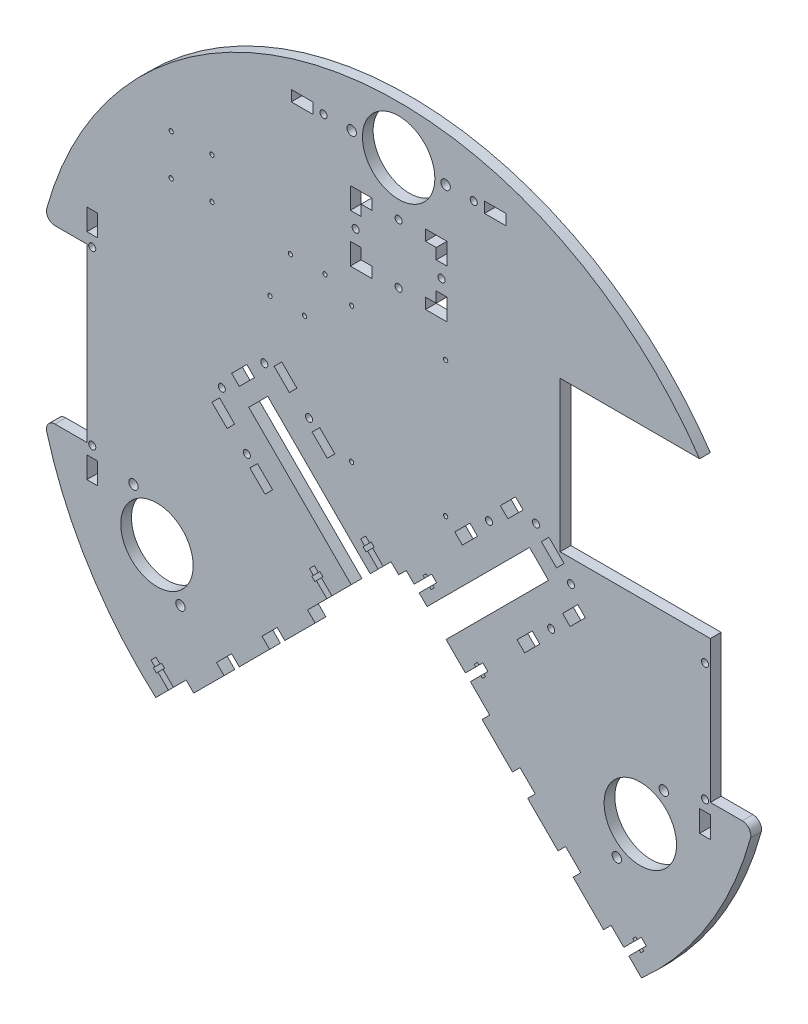
SolidWorks part; units mm, degrees
ref_plane "Front Plane" through (0, 0, 0) normal (0, 0, 1) x (1, 0, 0)
ref_plane "Top Plane" through (0, 0, 0) normal (0, 1, 0) x (1, 0, 0)
ref_plane "Right Plane" through (0, 0, 0) normal (1, 0, 0) x (0, 0, -1)
sketch "Sketch1" plane through (0, 0, 0) normal (0, 0, 1) x (1, 0, 0)
  circle A0 centre (0, 0) radius 215.9
  dimension "D1" = 431.8
extrude "Base Plate Extrusion" add sketch "Sketch1" along normal blind 6.35
sketch "Sketch2" plane through (0, 0, 6.35) normal (0, 0, 1) x (1, 0, 0)
  line L0 (0, 0) -> (0, -230.9791) construction
  line L1 (0, -17.4608) -> (143.6841, -161.1449)
  line L2 (0, -17.4608) -> (-143.6841, -161.1449)
  circle A1 centre (0, 0) radius 215.9 construction
  arc A2 (143.6841, -161.1449) -> (-143.6841, -161.1449) centre (0, 0) cw
  dimension "D1" = 90
  dimension "D2" = 203.2
extrude "V Funnel Cut" cut sketch "Sketch2" against normal through all
sketch "Sketch3" plane through (0, 0, 6.35) normal (0, 0, 1) x (1, 0, 0)
  line L0 (0, 0) -> (251.7982, 0) construction
  line L1 (209.8384, 50.8) -> (184.4384, 50.8)
  line L2 (209.8384, 50.8) -> (209.8384, -50.8)
  line L3 (209.8384, -50.8) -> (184.4384, -50.8)
  line L4 (184.4384, 50.8) -> (184.4384, -50.8)
  arc A0 (143.6841, -161.1449) -> (-143.6841, -161.1449) centre (0, 0) ccw construction
  arc A1 (209.8384, 50.8) -> (209.8384, -50.8) centre (0, 0) cw
  arc M7 (143.6841, -161.1449) -> (-143.6841, -161.1449) centre (0, 0) ccw
  dimension "D1" = 25.4
  dimension "D2" = 101.6
extrude "Wheel Track Cut" cut sketch "Sketch3" against normal through all contours L2 L0 A1 | L4 L0 L2 L1 | L0 L4 L3 L2 | L0 L2 M7 region at (197.1384, 25.4, 6.35) region at (197.1384, -25.4, 6.35) region at (212.266, 19.0862, 6.35) region at (212.266, -19.0862, 6.35)
mirror "Wheel Track Cut Mirror" about plane through (0, 0, 0) normal (1, 0, 0) of "Wheel Track Cut"
sketch "Sketch4" plane through (0, 0, 6.35) normal (0, 0, 1) x (1, 0, 0)
  line L0 (88.68, 15.0926) -> (77.4547, 26.3179)
  line L1 (88.68, 15.0926) -> (28.0633, -45.5241)
  line L2 (77.4547, 26.3179) -> (16.838, -34.2988)
  line L3 (28.0633, -45.5241) -> (16.838, -34.2988)
  line L4 (84.3174, 21.9553) -> (56.956, -5.4061) construction
  line L5 (65.1069, -1.7454) -> (69.5826, 2.7303) construction
  line L6 (65.0924, 7.2204) -> (60.6167, 2.7447) construction
  line L7 (143.6841, -161.1449) -> (0, -17.4608) construction
  dimension "D1" = 15.875
  dimension "D2" = 85.725
extrude "Silo Picker Clearance" cut sketch "Sketch4" against normal through all
sketch "Sketch5" plane through (0, 0, 6.35) normal (0, 0, 1) x (1, 0, 0)
  line L0 (-4.4901, -21.951) -> (0, -17.4608)
  line L1 (-4.4901, -21.951) -> (0, -26.4411)
  line L2 (0, -17.4608) -> (4.4901, -21.951)
  line L3 (0, -26.4411) -> (4.4901, -21.951)
  line L4 (0, -17.4608) -> (-143.6841, -161.1449) construction
  line L6 (4.4901, -21.951) -> (0, -26.4411) construction
  dimension "D1" = 6.35
extrude "V Funnel Corner" add sketch "Sketch5" against normal up to surface (6.35 mm away) up to face at (14.0691, -14.8765, 0)
mirror "Dump Picker Clearance" about plane through (0, 0, 0) normal (1, 0, 0) of "Silo Picker Clearance"
sketch "Sketch6" plane through (8.7304, -8.7304, 0) normal (0.7071, -0.7071, 0) x (0, 0, -1)
  line L0 (-6.35, -52.0342) -> (-6.35, -215.5467) construction
  line L1 (-6.35, -190.1467) -> (0, -190.1467)
  line L2 (-6.35, -190.1467) -> (-6.35, -164.7467)
  line L3 (-6.35, -164.7467) -> (0, -164.7467)
  line L4 (0, -190.1467) -> (0, -164.7467)
  line L5 (0, -52.0342) -> (0, -215.5467) construction
  dimension "D1" = 25.4
  dimension "D2" = 25.4
extrude "V Funnel Tab Left" add sketch "Sketch6" along normal blind 6.35
pattern_linear "V Funnel Tab Pattern Left" count 3 spacing 38.1 along (0.7071, 0.7071, 0) of "V Funnel Tab Left"
sketch "Sketch7" plane through (-8.7304, -8.7304, 0) normal (-0.7071, -0.7071, 0) x (0, 0, 1)
  line L0 (6.35, -215.5467) -> (6.35, -52.0342) construction
  line L1 (6.35, -164.7467) -> (0, -164.7467)
  line L2 (6.35, -164.7467) -> (6.35, -190.1467)
  line L3 (6.35, -190.1467) -> (0, -190.1467)
  line L4 (0, -164.7467) -> (0, -190.1467)
  line L5 (0, -215.5467) -> (0, -52.0342) construction
  dimension "D1" = 25.4
  dimension "D2" = 25.4
extrude "V Funnel Tab Right" add sketch "Sketch7" along normal blind 6.35
pattern_linear "V Funnel Tab Pattern Right" count 3 spacing 38.1 along (-0.7071, 0.7071, 0) of "V Funnel Tab Right"
sketch "Sketch8" plane through (0, 0, 0) normal (0, 0, -1) x (-1, 0, 0)
  line L0 (-70.046, -24.645) -> (-79.0263, -15.6648)
  line L1 (-79.0263, -15.6648) -> (-83.5164, -20.1549)
  line L2 (-83.5164, -20.1549) -> (-74.5361, -29.1352)
  line L3 (-74.5361, -29.1352) -> (-70.046, -24.645)
  line L4 (-96.9868, 2.2957) -> (-101.4769, -2.1944)
  line L5 (-101.4769, -2.1944) -> (-110.4572, 6.7859)
  line L6 (-110.4572, 6.7859) -> (-105.967, 11.276)
  line L7 (-105.967, 11.276) -> (-96.9868, 2.2957)
  line L8 (-97.8965, 28.3267) -> (-88.9163, 37.307)
  line L9 (-88.9163, 37.307) -> (-84.4262, 32.8169)
  line L10 (-84.4262, 32.8169) -> (-93.4064, 23.8366)
  line L11 (-93.4064, 23.8366) -> (-97.8965, 28.3267)
  line L12 (-64.6578, 34.6246) -> (-60.1677, 39.1148)
  line L13 (-60.1677, 39.1148) -> (-69.148, 48.095)
  line L14 (-69.148, 48.095) -> (-73.6381, 43.6049)
  line L15 (-73.6381, 43.6049) -> (-64.6578, 34.6246)
  line L16 (-46.6973, 16.6641) -> (-42.2072, 21.1543)
  line L17 (-42.2072, 21.1543) -> (-33.2269, 12.174)
  line L18 (-33.2269, 12.174) -> (-37.7171, 7.6839)
  line L19 (-37.7171, 7.6839) -> (-46.6973, 16.6641)
  line L20 (-105.967, 11.276) -> (-110.4572, 6.7859) construction
  line L21 (-69.148, 48.095) -> (-73.6381, 43.6049) construction
extrude "Silo Arm Tab Holes" cut sketch "Sketch8" against normal blind 6.35
sketch "Sketch10" plane through (0, 0, 0) normal (0, 0, -1) x (-1, 0, 0)
  line L0 (51.1875, 21.1543) -> (42.2072, 12.174)
  line L1 (42.2072, 12.174) -> (37.7171, 16.6641)
  line L2 (37.7171, 16.6641) -> (46.6973, 25.6444)
  line L3 (46.6973, 25.6444) -> (51.1875, 21.1543)
  line L4 (64.6578, 34.6246) -> (60.1677, 39.1148)
  line L5 (60.1677, 39.1148) -> (69.148, 48.095)
  line L6 (69.148, 48.095) -> (73.6381, 43.6049)
  line L7 (73.6381, 43.6049) -> (64.6578, 34.6246)
  line L8 (89.8026, 36.4207) -> (85.3124, 31.9306)
  line L9 (85.3124, 31.9306) -> (94.2927, 22.9503)
  line L10 (94.2927, 22.9503) -> (98.7828, 27.4404)
  line L11 (98.7828, 27.4404) -> (89.8026, 36.4207)
  line L12 (105.967, 11.276) -> (96.9868, 2.2957)
  line L13 (96.9868, 2.2957) -> (101.4769, -2.1944)
  line L14 (101.4769, -2.1944) -> (110.4572, 6.7859)
  line L15 (110.4572, 6.7859) -> (105.967, 11.276)
  line L16 (88.0065, -15.6648) -> (83.5164, -11.1747)
  line L17 (83.5164, -11.1747) -> (74.5361, -20.1549)
  line L18 (74.5361, -20.1549) -> (79.0263, -24.645)
  line L19 (79.0263, -24.645) -> (88.0065, -15.6648)
  line L20 (37.7171, 16.6641) -> (42.2072, 12.174) construction
  line L21 (74.5361, -20.1549) -> (79.0263, -24.645) construction
extrude "Dump Arm Tab Holes" cut sketch "Sketch10" against normal blind 6.35
sketch "Sketch11" plane through (0, 0, 0) normal (0, 0, -1) x (-1, 0, 0)
  line L1 (184.4384, -69.85) -> (178.0884, -69.85)
  line L2 (184.4384, -69.85) -> (184.4384, -57.15)
  line L3 (184.4384, -57.15) -> (178.0884, -57.15)
  line L4 (178.0884, -69.85) -> (178.0884, -57.15)
  line L5 (184.4384, 57.15) -> (178.0884, 57.15)
  line L6 (184.4384, 57.15) -> (184.4384, 69.85)
  line L7 (184.4384, 69.85) -> (178.0884, 69.85)
  line L8 (178.0884, 57.15) -> (178.0884, 69.85)
  line L9 (-178.0884, -69.85) -> (-184.4384, -69.85)
  line L10 (-178.0884, -69.85) -> (-178.0884, -57.15)
  line L11 (-178.0884, -57.15) -> (-184.4384, -57.15)
  line L12 (-184.4384, -69.85) -> (-184.4384, -57.15)
  line L13 (-178.0884, 57.15) -> (-184.4384, 57.15)
  line L14 (-178.0884, 57.15) -> (-178.0884, 69.85)
  line L15 (-178.0884, 69.85) -> (-184.4384, 69.85)
  line L16 (-184.4384, 57.15) -> (-184.4384, 69.85)
extrude "Wheel Support Tab Holes" cut sketch "Sketch11" against normal blind 6.35
sketch "Sketch13" plane through (0, 0, 6.35) normal (0, 0, 1) x (1, 0, 0)
  circle A0 centre (0, 187.325) radius 21.4313
  circle A1 centre (27.7812, 187.325) radius 2.7781
  circle A2 centre (-27.7813, 187.325) radius 2.7781
  dimension "D1" = 42.8625
  dimension "D2" = 5.5562
extrude "Caster Wheel Hole" cut sketch "Sketch13" against normal through all
sketch "Sketch14" plane through (0, 0, 6.35) normal (0, 0, 1) x (1, 0, 0)
  line L0 (184.4384, 48.6664) -> (178.0884, 52.9336) construction
  line L1 (184.4384, 50.8) -> (184.4384, -50.8) construction
  line L2 (178.0884, 48.6664) -> (184.4384, 48.6664) construction
  line L3 (184.4384, 52.9336) -> (178.0884, 48.6664) construction
  line L4 (184.4384, -52.9336) -> (178.0884, -48.6664) construction
  line L5 (184.4384, -48.6664) -> (178.0884, -52.9336) construction
  line L6 (178.0884, -48.6664) -> (184.4384, -48.6664) construction
  circle A0 centre (181.2634, 50.8) radius 2.0955
  circle A1 centre (181.2634, -50.8) radius 2.0955
  dimension "D1" = 4.191
extrude "Wheel Support Hole" cut sketch "Sketch14" against normal through all
mirror "Wheel Support Hole Mirror" about plane through (0, 0, 0) normal (1, 0, 0) of "Wheel Support Hole"
sketch "Sketch15" plane through (0, 0, 6.35) normal (0, 0, 1) x (1, 0, 0)
  line L0 (-134.7038, -152.1647) -> (-152.6084, -134.2601) construction
  line L1 (-125.7236, -143.1844) -> (-143.6841, -161.1449) construction
  line L2 (-40.9724, -58.4333) -> (-60.7132, -38.6924) construction
  line L3 (-28.0633, -45.5241) -> (-53.8815, -71.3424) construction
  line L4 (-10.6641, -28.1249) -> (-27.2834, -11.5055) construction
  line L5 (-4.4901, -21.951) -> (-16.838, -34.2988) construction
  line B0 (-136.1856, -153.6464) -> (-133.2221, -150.6829)
  line B1 (-141.2145, -142.6905) -> (-140.2716, -141.7476)
  line B2 (-140.2716, -141.7476) -> (-138.4755, -143.5436)
  line B3 (-138.4755, -143.5436) -> (-139.4185, -144.4866)
  line B4 (-139.4185, -144.4866) -> (-133.2221, -150.6829)
  line B5 (-141.2145, -142.6905) -> (-143.5494, -140.3556)
  line B6 (-143.5494, -140.3556) -> (-146.5129, -143.3191)
  line B7 (-144.178, -145.654) -> (-146.5129, -143.3191)
  line B8 (-142.382, -147.45) -> (-136.1856, -153.6464)
  line B9 (-143.3249, -148.393) -> (-142.382, -147.45)
  line B10 (-145.1209, -146.5969) -> (-143.3249, -148.393)
  line B11 (-144.178, -145.654) -> (-145.1209, -146.5969)
  line B12 (-42.4542, -59.915) -> (-39.4907, -56.9515)
  line B13 (-47.4831, -48.9591) -> (-46.5402, -48.0162)
  line B14 (-46.5402, -48.0162) -> (-44.7441, -49.8122)
  line B15 (-44.7441, -49.8122) -> (-45.6871, -50.7551)
  line B16 (-45.6871, -50.7551) -> (-39.4907, -56.9515)
  line B17 (-47.4831, -48.9591) -> (-49.818, -46.6242)
  line B18 (-49.818, -46.6242) -> (-52.7815, -49.5877)
  line B19 (-50.4466, -51.9226) -> (-52.7815, -49.5877)
  line B20 (-48.6505, -53.7186) -> (-42.4542, -59.915)
  line B21 (-49.5935, -54.6615) -> (-48.6505, -53.7186)
  line B22 (-51.3895, -52.8655) -> (-49.5935, -54.6615)
  line B23 (-50.4466, -51.9226) -> (-51.3895, -52.8655)
  line B24 (-12.1458, -29.6066) -> (-9.1823, -26.6431)
  line B25 (-17.1747, -18.6507) -> (-16.2318, -17.7078)
  line B26 (-16.2318, -17.7078) -> (-14.4358, -19.5038)
  line B27 (-14.4358, -19.5038) -> (-15.3787, -20.4468)
  line B28 (-15.3787, -20.4468) -> (-9.1823, -26.6431)
  line B29 (-17.1747, -18.6507) -> (-19.5096, -16.3159)
  line B30 (-19.5096, -16.3159) -> (-22.4731, -19.2793)
  line B31 (-20.1382, -21.6142) -> (-22.4731, -19.2793)
  line B32 (-18.3422, -23.4103) -> (-12.1458, -29.6066)
  line B33 (-19.2851, -24.3532) -> (-18.3422, -23.4103)
  line B34 (-21.0812, -22.5571) -> (-19.2851, -24.3532)
  line B35 (-20.1382, -21.6142) -> (-21.0812, -22.5571)
sketch_block_instance "TSlot-1"
sketch_block "TSlot" parameters "D1"=3.302, "D2"=2.54, "D3"=3.175, "D4"=8.763, "D5"=1.3462
sketch_block_instance "TSlot-3"
sketch_block_instance "TSlot-4"
extrude "V Funnel T Slot Cut Out" cut sketch "Sketch15" against normal through all
mirror "V Funnel T Slot Cut Out Mirror" about plane through (0, 0, 0) normal (1, 0, 0) of "V Funnel T Slot Cut Out"
sketch "Sketch19" plane through (0, 0, 6.35) normal (0, 0, 1) x (1, 0, 0)
  line L0 (46.5836, 190.5) -> (42.3164, 184.15) construction
  line L1 (46.5836, 184.15) -> (42.3164, 190.5) construction
  line L2 (-42.3164, 190.5) -> (-46.5836, 184.15) construction
  line L3 (-42.3164, 184.15) -> (-46.5836, 190.5) construction
  circle A0 centre (44.45, 187.325) radius 2.0955
  circle A1 centre (-44.45, 187.325) radius 2.0955
  dimension "D1" = 4.191
extrude "Switch Plate Holes" cut sketch "Sketch19" against normal through all
sketch "Sketch20" plane through (0, 0, 0) normal (0, 0, -1) x (-1, 0, 0)
  line L1 (-50.8, 184.15) -> (-63.5, 184.15)
  line L2 (-50.8, 184.15) -> (-50.8, 190.5)
  line L3 (-50.8, 190.5) -> (-63.5, 190.5)
  line L4 (-63.5, 184.15) -> (-63.5, 190.5)
  line L5 (63.5, 184.15) -> (50.8, 184.15)
  line L6 (63.5, 184.15) -> (63.5, 190.5)
  line L7 (63.5, 190.5) -> (50.8, 190.5)
  line L8 (50.8, 184.15) -> (50.8, 190.5)
extrude "Swith Plate Tab Holes" cut sketch "Sketch20" against normal through all
sketch "Sketch26" plane through (0, 0, 6.35) normal (0, 0, 1) x (1, 0, 0)
  line L0 (89.5152, -5.1758) -> (90.988, -12.6833) construction
  line L1 (86.4978, -8.1932) -> (94.0053, -9.666) construction
  line L2 (52.6961, 31.6432) -> (54.1689, 24.1357) construction
  line L3 (49.6788, 28.6258) -> (57.1863, 27.1531) construction
  line L4 (105.6855, 20.5377) -> (98.178, 19.065) construction
  line L5 (102.6682, 23.5551) -> (101.1954, 16.0476) construction
  line L6 (82.0136, 44.2097) -> (80.5408, 36.7022) construction
  line L7 (85.0309, 41.1923) -> (77.5234, 39.7196) construction
  circle A0 centre (90.2516, -8.9296) radius 2.0955
  circle A1 centre (53.4325, 27.8895) radius 2.0955
  circle A2 centre (101.9318, 19.8014) radius 2.0955
  circle A3 centre (81.2772, 40.4559) radius 2.0955
  dimension "D1" = 4.191
extrude "Silo Arm Holes" cut sketch "Sketch26" against normal through all
sketch "Sketch27" plane through (0, 0, 6.35) normal (0, 0, 1) x (1, 0, 0)
  line L0 (-49.2298, 28.1768) -> (-56.7373, 26.7041) construction
  line L1 (-52.2471, 31.1942) -> (-53.7199, 23.6867) construction
  line L2 (-80.2116, 46.0116) -> (-78.7389, 38.5041) construction
  line L3 (-83.229, 42.9942) -> (-75.7215, 41.5215) construction
  line L4 (-105.3564, 20.8669) -> (-103.8836, 13.3594) construction
  line L5 (-108.3737, 17.8495) -> (-100.8662, 16.3768) construction
  line L6 (-93.5563, -10.115) -> (-86.0488, -8.6422) construction
  line L7 (-90.5389, -13.1324) -> (-89.0662, -5.6249) construction
  circle A0 centre (-52.9835, 27.4404) radius 2.0955
  circle A1 centre (-79.4753, 42.2579) radius 2.0955
  circle A2 centre (-104.62, 17.1131) radius 2.0955
  circle A3 centre (-89.8026, -9.3786) radius 2.0955
  dimension "D1" = 4.191
extrude "Dump Arm Holes" cut sketch "Sketch27" against normal through all
fillet "Wheel Slot Fillet" radius 5.08 4 edges at (209.8384, -50.8, 3.175) (209.8384, 50.8, 3.175) (-209.8384, -50.8, 3.175) (-209.8384, 50.8, 3.175)
sketch "Sketch28" plane through (0, 0, 6.35) normal (0, 0, 1) x (1, 0, 0)
  line L0 (0, 0) -> (0, 258.9974) construction
  line L1 (0, 0) -> (249.4479, -144.0188) construction
  line L2 (0, 0) -> (-249.719, -144.1753) construction
  line L3 (-142.9808, -82.55) -> (-156.8714, -58.4907) construction
  line L4 (-27.7813, 187.325) -> (0, 187.325) construction
  line L5 (-142.9808, -82.55) -> (-129.0902, -106.6093) construction
  circle A0 centre (-142.9808, -82.55) radius 21.4313
  circle A1 centre (0, 187.325) radius 21.4313 construction
  circle A2 centre (-156.8714, -58.4907) radius 2.7781
  circle A3 centre (-27.7813, 187.325) radius 2.7781 construction
  circle A4 centre (-129.0902, -106.6093) radius 2.7781
  dimension "D1" = 120
  dimension "D2" = 120
  dimension "D3" = 165.1
extrude "Front Caster Holes" cut sketch "Sketch28" against normal through all
mirror "Front Caster Hole Mirror" about plane through (0, 0, 0) normal (1, 0, 0) of "Front Caster Holes"
sketch "Gyro Holes" plane through (0, 0, 6.35) normal (0, 0, 1) x (1, 0, 0)
  line L1 (-134.5682, 109.4626) -> (-110.4382, 109.4626) construction
  line L2 (-134.5682, 109.4626) -> (-134.5682, 133.5926) construction
  line L3 (-134.5682, 133.5926) -> (-110.4382, 133.5926) construction
  line L4 (-110.4382, 109.4626) -> (-110.4382, 133.5926) construction
  line L5 (-134.5682, 109.4626) -> (-110.4382, 133.5926) construction
  line L6 (-134.5682, 133.5926) -> (-110.4382, 109.4626) construction
  circle A0 centre (-134.5682, 133.5926) radius 1.27
  circle A1 centre (-110.4382, 133.5926) radius 1.27
  circle A2 centre (-110.4382, 109.4626) radius 1.27
  circle A3 centre (-134.5682, 109.4626) radius 1.27
  point P0 (-122.5032, 121.5276)
  dimension "D2" = 24.13
  dimension "D1" = 2.54
extrude "GyroHoles" cut sketch "Gyro Holes" against normal through all
sketch "MotorControllerHoleSketch" plane through (0, 0, 6.35) normal (0, 0, 1) x (1, 0, 0)
  line L0 (0, 215.9) -> (0, -26.4411) construction
  line L2 (-27.82, 17.5746) -> (27.82, 17.5746) construction
  line L3 (-27.82, 17.5746) -> (-27.82, 97.6146) construction
  line L4 (-27.82, 97.6146) -> (27.82, 97.6146) construction
  line L5 (27.82, 17.5746) -> (27.82, 97.6146) construction
  line L6 (-27.82, 17.5746) -> (27.82, 97.6146) construction
  line L7 (-27.82, 97.6146) -> (27.82, 17.5746) construction
  arc A0 (208.1777, 57.2265) -> (-208.1777, 57.2265) centre (0, 0) ccw construction
  circle A1 centre (-27.82, 97.6146) radius 1.25
  circle A2 centre (27.82, 97.6146) radius 1.25
  circle A3 centre (27.82, 17.5746) radius 1.25
  circle A4 centre (-27.82, 17.5746) radius 1.25
  point P6 (0, 57.5946)
  dimension "D1" = 2.5
  dimension "D2" = 55.64
  dimension "D3" = 80.04
extrude "Motor Controller Hole" cut sketch "MotorControllerHoleSketch" against normal through all
sketch "Sketch31" plane through (0, 0, 6.35) normal (0, 0, 1) x (1, 0, 0)
  line L0 (-59.8452, 118.6025) -> (-59.8452, 61.2016) construction
  line L1 (-43.5402, 78.4228) -> (-55.6734, 78.4228) construction
  line L2 (-43.5402, 78.4228) -> (-43.5402, 105.8377) construction
  line L3 (-43.5402, 105.8377) -> (-55.6734, 105.8377) construction
  line L4 (-55.6734, 78.4228) -> (-55.6734, 105.8377) construction
  line L5 (-43.5402, 78.4228) -> (-55.6734, 105.8377) construction
  line L6 (-43.5402, 105.8377) -> (-55.6734, 78.4228) construction
  line L7 (-64.017, 78.4228) -> (-76.1502, 78.4228) construction
  line L8 (-64.017, 78.4228) -> (-64.017, 105.8377) construction
  line L9 (-64.017, 105.8377) -> (-76.1502, 105.8377) construction
  line L10 (-76.1502, 78.4228) -> (-76.1502, 105.8377) construction
  line L11 (-64.017, 78.4228) -> (-76.1502, 105.8377) construction
  line L12 (-64.017, 105.8377) -> (-76.1502, 78.4228) construction
  line L13 (-70.0836, 92.1303) -> (-49.6068, 92.1303) construction
  circle A0 centre (-76.1502, 78.4228) radius 1.27
  circle A1 centre (-64.017, 105.8377) radius 1.27
  circle A2 centre (-55.6734, 78.4228) radius 1.27
  circle A3 centre (-43.5402, 105.8377) radius 1.27
  point P0 (-49.6068, 92.1303)
  point P5 (-70.0836, 92.1303)
  dimension "D1" = 2.54
extrude "BuckConverterHoles" cut sketch "Sketch31" against normal through all
sketch "Sketch34" plane through (0, 0, 0) normal (0, 0, -1) x (-1, 0, 0)
  line L1 (-28.575, 158.75) -> (-15.875, 158.75)
  line L2 (-28.575, 158.75) -> (-28.575, 152.4)
  line L3 (-22.225, 152.4) -> (-15.875, 152.4)
  line L4 (-15.875, 158.75) -> (-15.875, 152.4)
  line L5 (15.875, 158.75) -> (28.575, 158.75)
  line L6 (15.875, 158.75) -> (15.875, 152.4)
  line L7 (15.875, 152.4) -> (22.225, 152.4)
  line L8 (28.575, 158.75) -> (28.575, 152.4)
  line L9 (15.875, 123.825) -> (22.225, 123.825)
  line L10 (15.875, 123.825) -> (15.875, 117.475)
  line L11 (15.875, 117.475) -> (28.575, 117.475)
  line L12 (28.575, 123.825) -> (28.575, 117.475)
  line L13 (-22.225, 123.825) -> (-15.875, 123.825)
  line L14 (-28.575, 123.825) -> (-28.575, 117.475)
  line L15 (-28.575, 117.475) -> (-15.875, 117.475)
  line L16 (-15.875, 123.825) -> (-15.875, 117.475)
  line L17 (-28.575, 130.175) -> (-22.225, 130.175)
  line L18 (-28.575, 130.175) -> (-28.575, 123.825)
  line L20 (-22.225, 130.175) -> (-22.225, 123.825)
  line L22 (-28.575, 152.4) -> (-28.575, 146.05)
  line L23 (-28.575, 146.05) -> (-22.225, 146.05)
  line L24 (-22.225, 152.4) -> (-22.225, 146.05)
  line L26 (22.225, 152.4) -> (22.225, 146.05)
  line L27 (22.225, 146.05) -> (28.575, 146.05)
  line L28 (28.575, 152.4) -> (28.575, 146.05)
  line L29 (22.225, 130.175) -> (28.575, 130.175)
  line L30 (22.225, 130.175) -> (22.225, 123.825)
  line L32 (28.575, 130.175) -> (28.575, 123.825)
extrude "Cut-Extrude6" cut sketch "Sketch34" against normal through all
sketch "Sketch35" plane through (0, 0, 6.35) normal (0, 0, 1) x (1, 0, 0)
  line L0 (-22.225, 136.017) -> (-28.575, 140.208) construction
  line L1 (-28.575, 136.017) -> (-22.225, 140.208) construction
  line L2 (-2.0955, 152.4) -> (2.0955, 158.75) construction
  line L3 (2.0955, 152.4) -> (-2.0955, 158.75) construction
  line L4 (22.225, 136.017) -> (28.575, 140.208) construction
  line L5 (22.225, 140.208) -> (28.575, 136.017) construction
  line L6 (2.0955, 123.825) -> (-2.0955, 117.475) construction
  line L7 (-2.0955, 123.825) -> (2.0955, 117.475) construction
  circle A0 centre (0, 120.65) radius 2.0955
  circle A1 centre (25.4, 138.1125) radius 2.0955
  circle A2 centre (0, 155.575) radius 2.0955
  circle A3 centre (-25.4, 138.1125) radius 2.0955
  dimension "D1" = 4.191
extrude "Cut-Extrude7" cut sketch "Sketch35" against normal through all
sketch "Sketch36" plane through (0, 0, 6.35) normal (0, 0, 1) x (1, 0, 0)
  line L0 (86.0134, 198.0265) -> (86.0134, 49.1901)
  line L1 (86.0134, 49.1901) -> (174.9134, 49.1901)
  line L2 (174.9134, 49.1901) -> (174.9134, 126.5626)
  line L3 (174.9134, 105.1417) -> (174.9134, 49.1901) construction
  line L4 (86.0134, 49.1901) -> (86.0134, 193.8168) construction
  arc A0 (208.1777, 57.2265) -> (-208.1777, 57.2265) centre (0, 0) ccw construction
  arc A1 (86.0134, 198.0265) -> (174.9134, 126.5626) centre (0, 0) cw
extrude "Cut-Extrude8" [suppressed] cut sketch "Sketch36" against normal through all
sketch "Sketch37" [suppressed] plane through (0, 0, 0) normal (0, 0, -1) x (-1, 0, 0)
  line L0 (-86.0134, 49.1901) -> (-174.9134, 49.1901) construction
  line L1 (-117.7634, 49.1901) -> (-143.1634, 49.1901)
  line L2 (-117.7634, 49.1901) -> (-117.7634, 55.5401)
  line L3 (-117.7634, 55.5401) -> (-143.1634, 55.5401)
  line L4 (-143.1634, 49.1901) -> (-143.1634, 55.5401)
  line L5 (-117.7634, 49.1901) -> (-117.7634, 55.5401) construction
extrude "Boss-Extrude1" [suppressed] add sketch "Sketch37" against normal up to surface (6.35 mm away) up to face at (-23.3045, 138.1125, 6.35)
sketch "Sketch38" plane through (0, 0, 0) normal (0, 0, -1) x (-1, 0, 0)
  line L2 (-186.392, 104.3946) -> (-275.292, 104.3946) construction
  line L4 (-143.1634, 55.5401) -> (-143.1634, 49.1901) construction
  line L5 (-268.942, 186.9446) -> (-268.942, 110.7446) construction
  line L7 (-192.742, 110.7446) -> (-192.742, 186.9446) construction
  line L8 (-117.7634, 49.1901) -> (-117.7634, 55.5401) construction
  line B0 (-153.1572, 104.3946) -> (-157.3482, 104.3946)
  line B1 (-157.3482, 93.0916) -> (-158.6817, 93.0916)
  line B2 (-158.6817, 93.0916) -> (-158.6817, 95.6316)
  line B3 (-158.6817, 95.6316) -> (-157.3482, 95.6316)
  line B4 (-157.3482, 95.6316) -> (-157.3482, 104.3946)
  line B5 (-157.3482, 93.0916) -> (-157.3482, 89.7896)
  line B6 (-157.3482, 89.7896) -> (-153.1572, 89.7896)
  line B7 (-153.1572, 93.0916) -> (-153.1572, 89.7896)
  line B8 (-153.1572, 95.6316) -> (-153.1572, 104.3946)
  line B9 (-151.8237, 95.6316) -> (-153.1572, 95.6316)
  line B10 (-151.8237, 93.0916) -> (-151.8237, 95.6316)
  line B11 (-153.1572, 93.0916) -> (-151.8237, 93.0916)
  line B12 (-155.2527, 104.3946) -> (-155.2527, 89.7896) construction
  line B13 (-203.9572, 104.3946) -> (-208.1482, 104.3946)
  line B14 (-208.1482, 93.0916) -> (-209.4817, 93.0916)
  line B15 (-209.4817, 93.0916) -> (-209.4817, 95.6316)
  line B16 (-209.4817, 95.6316) -> (-208.1482, 95.6316)
  line B17 (-208.1482, 95.6316) -> (-208.1482, 104.3946)
  line B18 (-208.1482, 93.0916) -> (-208.1482, 89.7896)
  line B19 (-208.1482, 89.7896) -> (-203.9572, 89.7896)
  line B20 (-203.9572, 93.0916) -> (-203.9572, 89.7896)
  line B21 (-203.9572, 95.6316) -> (-203.9572, 104.3946)
  line B22 (-202.6237, 95.6316) -> (-203.9572, 95.6316)
  line B23 (-202.6237, 93.0916) -> (-202.6237, 95.6316)
  line B24 (-203.9572, 93.0916) -> (-202.6237, 93.0916)
  line B25 (-206.0527, 104.3946) -> (-206.0527, 89.7896) construction
sketch_block_instance "TSlot-5"
sketch_block_instance "TSlot-6"
extrude "Cut-Extrude9" [suppressed] cut sketch "Sketch38" against normal through all
fillet "Fillet1" [suppressed] radius 6.35
sketch "Sketch39" plane through (0, 0, 0) normal (0, 0, -1) x (-1, 0, 0)
  line L0 (-184.4384, 33.1763) -> (-227.6876, 33.1763)
  line L1 (-95.5384, 33.1763) -> (-184.4384, 33.1763)
  line L2 (-95.5384, 33.1763) -> (-95.5384, 122.0763)
  line L3 (-95.5384, 122.0763) -> (-184.4384, 122.0763)
  arc A0 (-227.6876, 33.1763) -> (-184.4384, 122.0763) centre (-22.9914, -11.4365) cw
extrude "Cut-Extrude11" cut sketch "Sketch39" against normal through all
sketch "Sketch40" plane through (0, 0, 6.35) normal (0, 0, 1) x (1, 0, 0)
  line L0 (178.0884, 21.1455) -> (184.4384, 16.9545) construction
  line L1 (184.4384, 33.1763) -> (184.4384, -50.8) construction
  line L2 (178.0884, 16.9545) -> (184.4384, 16.9545) construction
  line L3 (178.0884, 16.9545) -> (184.4384, 21.1455) construction
  circle A0 centre (181.2634, 19.05) radius 2.0955
  dimension "D1" = 4.191
extrude "Cut-Extrude12" cut sketch "Sketch40" against normal through all
